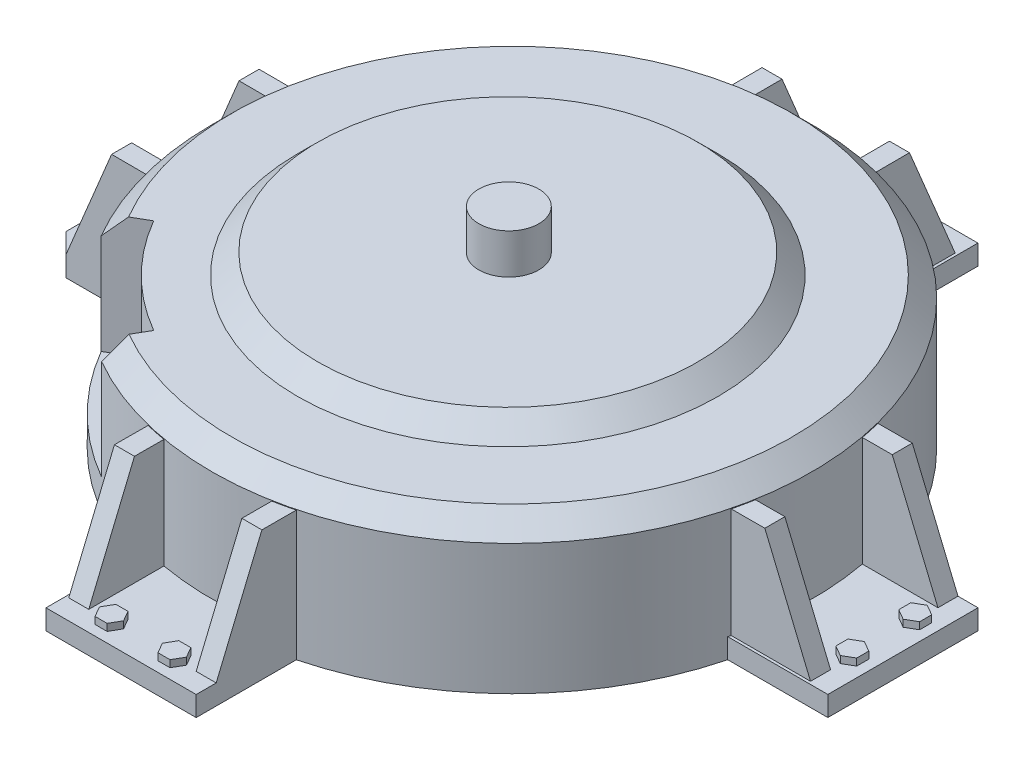
SolidWorks part; units mm, degrees
ref_plane "Front Plane" through (0, 0, 0) normal (0, 0, 1) x (1, 0, 0)
ref_plane "Top Plane" through (0, 0, 0) normal (0, 1, 0) x (1, 0, 0)
ref_plane "Right Plane" through (0, 0, 0) normal (1, 0, 0) x (0, 0, -1)
sketch "Sketch2" plane through (0, 0, 0) normal (0, 1, 0) x (1, 0, 0)
  circle A0 centre (0.7055, 0.7055) radius 150
  dimension "D1" = 300
extrude "Boss-Extrude1" add sketch "Sketch2" along normal blind 75
chamfer "Chamfer1" distance 10 angle 45 1 edges at (0.7055, 75, 149.2945)
sketch "Sketch3" plane through (0, 0, 0) normal (0, -1, 0) x (1, 0, 0)
  line L1 (1.6493, 0.0089) -> (188.7133, 0.0089)
  line L3 (-144.5379, -38.1804) -> (-194.5249, -38.1804)
  line L5 (-144.5249, 36.8196) -> (-194.5249, 36.8196)
  line L6 (-194.5249, -38.1804) -> (-194.5249, 36.8196)
  circle A0 centre (0.7055, -0.7055) radius 150 construction
  arc A1 (-144.5379, -38.1804) -> (-144.5249, 36.8196) centre (0.7055, -0.7055) ccw
  point P4 (-149.0491, -0.6804)
  circle M6 centre (0.7055, -0.7055) radius 150
  dimension "D1" = 50
extrude "Boss-Extrude2" add sketch "Sketch3" against normal blind 10 contours L6 L3 L5 M6 region at (-171.0995, 0, -0.6787)
chamfer "Chamfer2" distance 10 angle 45 2 edges at (-194.5249, 5, -38.1804) (-194.5249, 5, 36.8196)
sketch "Sketch4" plane through (0, 0, 36.8196) normal (0, 0, 1) x (1, 0, 0)
  line L0 (-144.3027, 9.9905) -> (-144.3027, 64.752)
  line L1 (-144.3027, 64.752) -> (-161.7058, 64.8027)
  line L2 (-161.7058, 64.8027) -> (-184.5247, 9.9999)
  line L3 (-184.5247, 9.9999) -> (-144.3027, 9.9905)
extrude "Boss-Extrude7" add sketch "Sketch4" against normal blind 10
sketch "Sketch5" plane through (0, 10, 0) normal (0, 1, 0) x (1, 0, 0)
  line L0 (-184.4705, 38.4292) -> (-184.2825, -51.6097) construction
  line L2 (-184.2825, -9.6918) -> (-189.4918, -12.6994)
  line L3 (-189.4918, -12.6994) -> (-189.4918, -18.7145)
  line L4 (-189.4918, -18.7145) -> (-184.2825, -21.7221)
  line L5 (-184.2825, -21.7221) -> (-179.0733, -18.7145)
  line L6 (-179.0733, -18.7145) -> (-179.0733, -12.6994)
  line L7 (-179.0733, -12.6994) -> (-184.2825, -9.6918)
  circle A0 centre (-184.2825, -15.707) radius 5.2093 construction
extrude "Boss-Extrude8" add sketch "Sketch5" along normal blind 3.5
mirror "Mirror1" about plane through (0, 0, 0) normal (0, 0, 1) of "Boss-Extrude8", "Boss-Extrude7"
pattern_circular "CirPattern1" count 4 over 360 about axis through (0.7055, 0, -0.7055) along (0, 1, 0) of "Boss-Extrude2", "Boss-Extrude7", "Mirror1"
sketch "Sketch6" plane through (0, 75, 0) normal (0, 1, 0) x (1, 0, 0)
  line L0 (0.11, -0.2547) -> (0.051, -0.2547) construction
  line L1 (0.051, -0.2547) -> (0.051, -0.4375) construction
  line L2 (0.0809, -0.2547) -> (-0.0624, -0.503)
  line L3 (0.4741, -0.1932) -> (-0.0624, -0.503)
  line L4 (0.051, -149.2931) -> (0.051, -161.0655) construction
  line L6 (-112.2462, -65.2724) -> (-128.8657, -74.8676)
  line L7 (-64.8267, -112.6781) -> (-74.3471, -129.1679)
  arc A0 (-112.2462, -65.2724) -> (-64.8267, -112.6781) centre (0.2651, -0.1478) ccw
  circle A1 centre (0.7055, 0.7055) radius 150 construction
  arc A2 (-128.8657, -74.8676) -> (-74.3471, -129.1679) centre (0.7055, 0.7055) ccw
  circle M7 centre (0.7055, 0.7055) radius 140
  dimension "D1" = 260
extrude "Cut-Extrude1" cut sketch "Sketch6" against normal blind 60 contours A0 L6 L7 M7 | L6 A2 L7 M7 region at (-93.8933, 75, 94.1875) region at (-100.5098, 75, 100.9306)
sketch "Sketch8" plane through (0, 75, 0) normal (0, 1, 0) x (1, 0, 0)
  circle A0 centre (-0.3338, -0.3338) radius 110
  dimension "D1" = 220
extrude "Boss-Extrude9" add sketch "Sketch8" along normal blind 10
chamfer "Chamfer3" distance 15 angle 45 1 edges at (-0.3338, 85, 110.3338)
sketch "Sketch9" plane through (0, 85, 0) normal (0, 1, 0) x (1, 0, 0)
  circle A0 centre (0.1858, -0.3338) radius 15
extrude "Boss-Extrude10" add sketch "Sketch9" along normal blind 20
